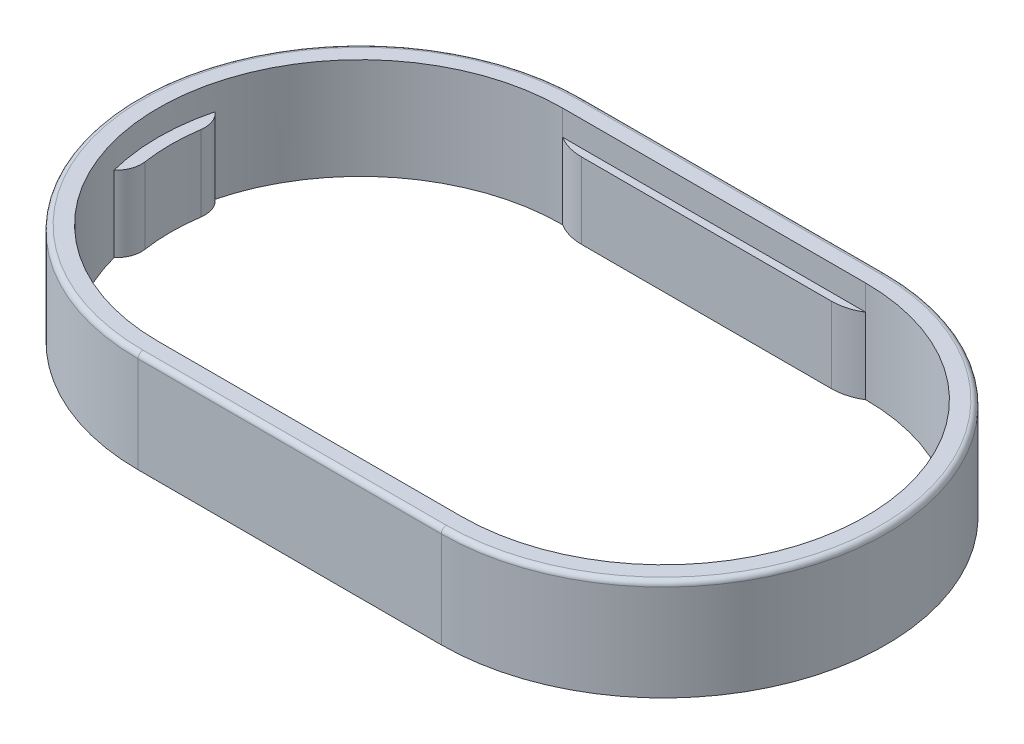
SolidWorks part; units mm, degrees
ref_plane "Front Plane" through (0, 0, 0) normal (0, 0, 1) x (1, 0, 0)
ref_plane "Top Plane" through (0, 0, 0) normal (0, 1, 0) x (1, 0, 0)
ref_plane "Right Plane" through (0, 0, 0) normal (1, 0, 0) x (0, 0, -1)
sketch "Sketch1" plane through (0, 0, 0) normal (0, 1, 0) x (1, 0, 0)
  line L0 (0, 0) -> (60, 0)
  line L1 (60, 88) -> (0, 88)
  arc A0 (60, 0) -> (60, 88) centre (60, 44) ccw
  arc A1 (0, 88) -> (0, 0) centre (0, 44) ccw
  dimension "D1" = 60
extrude "Boss-Extrude1" add sketch "Sketch1" along normal blind 20
shell "Shell1" thickness 4 removed face at (30, 0, -44) removed face at (30, 20, -44)
sketch "Sketch3" plane through (0, 0, 0) normal (0, -1, 0) x (1, 0, 0)
  line L0 (0, -4) -> (0, -5.5)
  line L1 (0, -5.5) -> (60, -5.5)
  line L2 (60, -5.5) -> (60, -4)
  line L3 (60, -4) -> (0, -4)
  dimension "D1" = 1.5
extrude "Boss-Extrude2" add sketch "Sketch3" against normal blind 15
sketch "Sketch5" plane through (0, 0, 0) normal (0, -1, 0) x (1, 0, 0)
  line L0 (0, -84) -> (0, -82.5)
  line L1 (0, -82.5) -> (60.0038, -82.5)
  line L2 (60.0038, -82.5) -> (60, -84)
  line L3 (60, -84) -> (0, -84)
extrude "Boss-Extrude3" add sketch "Sketch5" against normal blind 15
fillet "Fillet2" radius 10 4 edges at (60, 7.5, -5.5) (60.0038, 7.5, -82.5) (0, 7.5, -82.5) (0, 7.5, -5.5)
sketch "Sketch7" plane through (0, 0, 0) normal (0, -1, 0) x (1, 0, 0)
  line L0 (30, 0) -> (30, -88) construction
  line L1 (0, 0) -> (60, 0) construction
  line L2 (60, -88) -> (0, -88) construction
  line L3 (-44, -44) -> (104, -44) construction
  line L4 (-64.1911, -22) -> (109.5184, -22) construction
  line L5 (-44, -44) -> (-42, -44) construction
  line L6 (-38.1051, -22) -> (-36.1051, -22) construction
  line L7 (0, 0) -> (0, -88) construction
  line L8 (0, 0) -> (0, -2) construction
  line L9 (0, -88) -> (0, -86) construction
  arc A0 (0, 0) -> (0, -88) centre (0, -44) ccw construction
  arc A1 (60, -88) -> (60, 0) centre (60, -44) ccw construction
  circle A2 centre (-42, -44) radius 1
  circle A3 centre (-36.1051, -22) radius 1
  circle A4 centre (-36.1051, -66) radius 1
  circle A5 centre (0, -2) radius 1
  circle A6 centre (30, -2) radius 1
  circle A7 centre (0, -86) radius 1
  circle A8 centre (30, -86) radius 1
  circle A9 centre (96.1051, -22) radius 1
  circle A11 centre (96.1051, -66) radius 1
  circle A12 centre (60, -86) radius 1
  circle A13 centre (60, -2) radius 1
  dimension "D1" = 22
sketch "Sketch8" plane through (0, 0, 0) normal (0, -1, 0) x (1, 0, 0)
  line L0 (100, -44) -> (60, -44) construction
  line L1 (30, -5.5) -> (30, -82.5) construction
  line L2 (5.2678, -5.5) -> (54.7322, -5.5) construction
  line L3 (54.7322, -82.5) -> (5.2678, -82.5) construction
  line L4 (35.9573, -34) -> (113.0034, -34) construction
  line L5 (35.9573, -54) -> (113.0034, -54) construction
  line L6 (96.1421, -34) -> (98.7298, -34)
  line L7 (96.1421, -54) -> (98.7298, -54)
  line L8 (-36.1421, -54) -> (-38.7298, -54)
  line L9 (-36.1421, -34) -> (-38.7298, -34)
  arc A0 (60, -84) -> (60, -4) centre (60, -44) ccw construction
  arc A1 (96.1421, -54) -> (96.1421, -34) centre (60, -44) ccw
  arc A2 (98.7298, -54) -> (98.7298, -34) centre (60, -44) ccw
  arc A3 (-38.7298, -54) -> (-38.7298, -34) centre (0, -44) cw
  arc A4 (-36.1421, -54) -> (-36.1421, -34) centre (0, -44) cw
  dimension "D1" = 10
extrude "Boss-Extrude5" add sketch "Sketch8" against normal blind 15
fillet "Fillet5" radius 5 4 edges at (96.1421, 7.5, -34) (96.1421, 7.5, -54) (-36.1421, 7.5, -34) (-36.1421, 7.5, -54)
fillet "Fillet6" radius 1 4 edges at (30, 20, -88) (104, 20, -44) (30, 20, 0) (-44, 20, -44)
extrude "Cut-Extrude1" cut sketch "Sketch7" against normal blind 3
